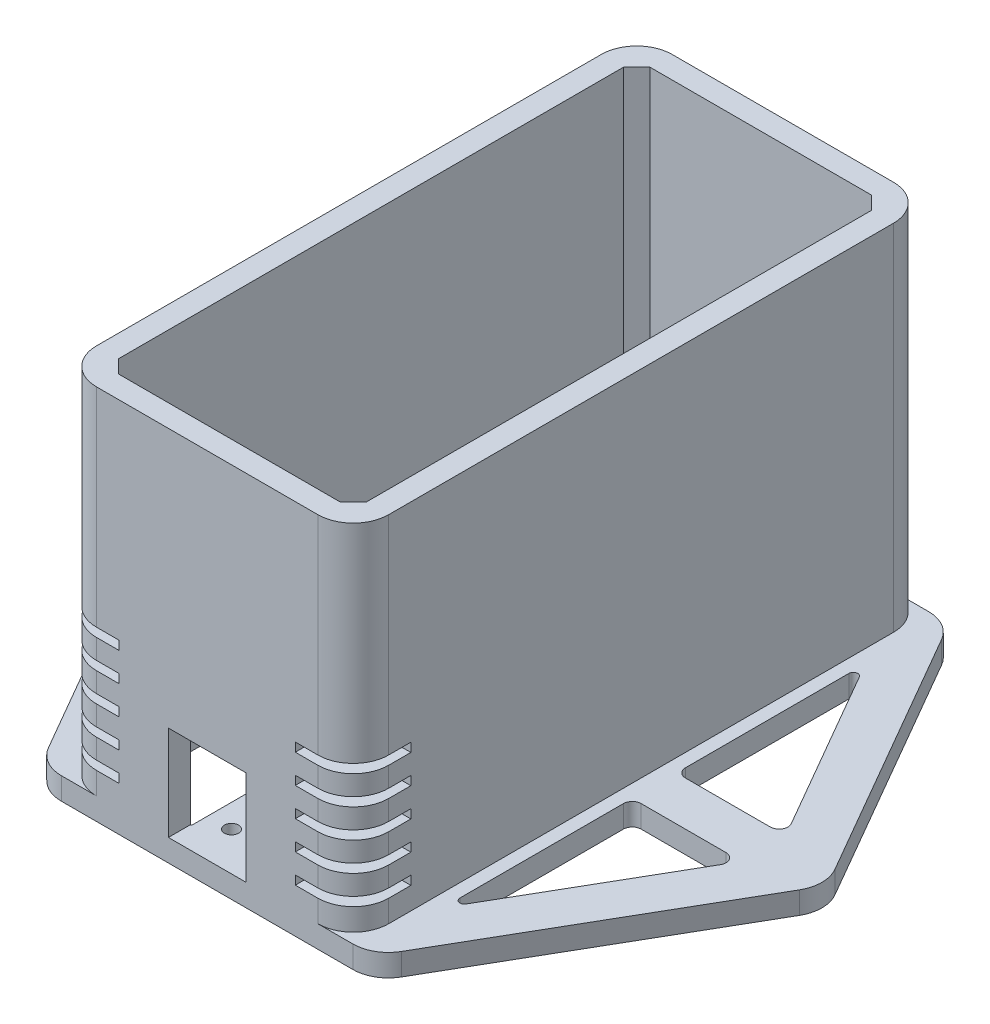
SolidWorks part; units mm, degrees
ref_plane "Front Plane" through (0, 0, 0) normal (0, 0, 1) x (1, 0, 0)
ref_plane "Top Plane" through (0, 0, 0) normal (0, 1, 0) x (1, 0, 0)
ref_plane "Right Plane" through (0, 0, 0) normal (1, 0, 0) x (0, 0, -1)
sketch "Sketch1" plane through (0, 0, 0) normal (0, 1, 0) x (1, 0, 0)
  line L1 (-75.0555, 0) -> (-37.5278, -65)
  line L2 (-37.5278, -65) -> (37.5278, -65)
  line L3 (37.5278, -65) -> (75.0555, 0)
  line L4 (75.0555, 0) -> (37.5278, 65)
  line L5 (37.5278, 65) -> (-37.5278, 65)
  line L6 (-37.5278, 65) -> (-75.0555, 0)
  circle A0 centre (0, 0) radius 65 construction
  circle A1 centre (0, 0) radius 50 construction
  dimension "D2" = 100
  dimension "D1" = 130
extrude "Boss-Extrude1" add sketch "Sketch1" along normal blind 5
fillet "Fillet1" radius 8 6 edges at (37.5278, 2.5, -65) (75.0555, 2.5, 0) (37.5278, 2.5, 65) (-37.5278, 2.5, 65) (-75.0555, 2.5, 0) (-37.5278, 2.5, -65)
sketch "Sketch3" plane through (0, 5, 0) normal (0, 1, 0) x (1, 0, 0)
  line L0 (-32.909, -65) -> (32.909, -65) construction
  line L1 (-25, 65) -> (25, 65)
  line L2 (-33, 57) -> (-33, -57)
  line L3 (-25, -65) -> (25, -65)
  line L4 (33, 57) -> (33, -57)
  line L5 (-33, 65) -> (33, -65) construction
  line L6 (-33, -65) -> (33, 65) construction
  arc A0 (33, 57) -> (25, 65) centre (25, 57) ccw
  arc A1 (33, -57) -> (25, -65) centre (25, -57) cw
  arc A2 (-25, -65) -> (-33, -57) centre (-25, -57) cw
  arc A3 (-25, 65) -> (-33, 57) centre (-25, 57) ccw
  point P0 (0, 0)
  dimension "D1" = 8
  dimension "D2" = 50
extrude "Boss-Extrude2" add sketch "Sketch3" along normal blind 80
sketch "Sketch4" plane through (0, 85, 0) normal (0, 1, 0) x (1, 0, 0)
  line L0 (-28, 57) -> (-25, 60)
  line L1 (25, 60) -> (28, 57)
  line L2 (28, -57) -> (25, -60)
  line L3 (-28, -57) -> (-25, -60)
  line L9 (-25, -60) -> (25, -60)
  line L10 (28, -57) -> (28, 57)
  line L11 (25, 60) -> (-25, 60)
  line L12 (-28, 57) -> (-28, -57)
  line L13 (-25, -60) -> (25, -60)
  line L14 (28, -57) -> (28, 57)
  line L15 (25, 60) -> (-25, 60)
  line L16 (-28, 57) -> (-28, -57)
  arc A9 (-28, -57) -> (-25, -60) centre (-25, -57) ccw
  arc A10 (25, -60) -> (28, -57) centre (25, -57) ccw
  arc A11 (28, 57) -> (25, 60) centre (25, 57) ccw
  arc A12 (-25, 60) -> (-28, 57) centre (-25, 57) ccw
  dimension "D1" = 5
extrude "Cut-Extrude1" cut sketch "Sketch4" against normal up to surface (85 mm away) up to face at (0, 0, 0)
sketch "Sketch8" plane through (0, 0, 0) normal (0, 1, 0) x (1, 0, 0)
  line L0 (0, 40) -> (0, 25) construction
  line L1 (0, 55) -> (0, 65) construction
  line L2 (9.5263, 26.5) -> (24.2487, 52) construction
  line L3 (22.5167, 55) -> (-22.5167, 55) construction
  line L4 (-24.2487, 52) -> (-9.5263, 26.5) construction
  line L5 (-12.5, 0) -> (-62.3346, 0) construction
  line L36 (6.9282, 25) -> (-6.9282, 25) construction
  line L37 (27.7128, 5) -> (57.1577, 5) construction
  line L38 (58.8897, 8) -> (36.3731, 47) construction
  line L39 (32.909, 47) -> (18.1865, 21.5) construction
  line L40 (25.1147, 6.5) -> (18.1865, 18.5) construction
  line L41 (18.1865, -21.5) -> (32.909, -47) construction
  line L42 (36.3731, -47) -> (58.8897, -8) construction
  line L43 (57.1577, -5) -> (27.7128, -5) construction
  line L44 (18.1865, -18.5) -> (25.1147, -6.5) construction
  line L45 (-9.5263, -26.5) -> (-24.2487, -52) construction
  line L46 (-22.5167, -55) -> (22.5167, -55) construction
  line L47 (24.2487, -52) -> (9.5263, -26.5) construction
  line L48 (-6.9282, -25) -> (6.9282, -25) construction
  line L49 (-27.7128, -5) -> (-57.1577, -5) construction
  line L50 (-58.8897, -8) -> (-36.3731, -47) construction
  line L51 (-32.909, -47) -> (-18.1865, -21.5) construction
  line L52 (-25.1147, -6.5) -> (-18.1865, -18.5) construction
  line L53 (-18.1865, 21.5) -> (-32.909, 47) construction
  line L54 (-37.866, 44.4141) -> (-58.8897, 8)
  line L55 (-57.1577, 5) -> (-38, 5)
  line L56 (-18.1865, 18.5) -> (-25.1147, 6.5) construction
  line L57 (-36, 7) -> (-36, 43.9141)
  line L58 (-33, 57) -> (-33, -57) construction
  line L59 (-36, -7) -> (-36, -43.9141)
  line L60 (-36.3731, 47) -> (-36, 47.6462) construction
  line L61 (-36, 5) -> (-27.7128, 5) construction
  line L71 (-33, 57) -> (-33, -57) construction
  line L72 (-57.1577, -5) -> (-38, -5)
  line L73 (-37.866, -44.4141) -> (-58.8897, -8)
  line L74 (37.866, -44.4141) -> (58.8897, -8)
  line L75 (57.1577, -5) -> (38, -5)
  line L76 (36, -7) -> (36, -43.9141)
  line L77 (36, 7) -> (36, 43.9141)
  line L78 (57.1577, 5) -> (38, 5)
  line L79 (37.866, 44.4141) -> (58.8897, 8)
  circle A0 centre (0, 0) radius 12.5 construction
  circle A1 centre (0, 40) radius 15 construction
  arc A3 (-22.5167, 55) -> (-24.2487, 52) centre (-22.5167, 53) ccw
  arc A4 (24.2487, 52) -> (22.5167, 55) centre (22.5167, 53) ccw construction
  arc A5 (6.9282, 25) -> (9.5263, 26.5) centre (6.9282, 28) ccw construction
  arc A6 (-6.9282, 25) -> (-9.5263, 26.5) centre (-6.9282, 28) cw construction
  arc A7 (25.1147, 6.5) -> (27.7128, 5) centre (27.7128, 8) ccw construction
  arc A8 (57.1577, 5) -> (58.8897, 8) centre (57.1577, 7) ccw construction
  arc A9 (36.3731, 47) -> (32.909, 47) centre (34.641, 46) ccw construction
  arc A10 (18.1865, 18.5) -> (18.1865, 21.5) centre (20.7846, 20) cw construction
  arc A11 (18.1865, -18.5) -> (18.1865, -21.5) centre (20.7846, -20) ccw construction
  arc A12 (32.909, -47) -> (36.3731, -47) centre (34.641, -46) ccw construction
  arc A13 (58.8897, -8) -> (57.1577, -5) centre (57.1577, -7) ccw construction
  arc A14 (25.1147, -6.5) -> (27.7128, -5) centre (27.7128, -8) cw construction
  arc A15 (-6.9282, -25) -> (-9.5263, -26.5) centre (-6.9282, -28) ccw construction
  arc A16 (-24.2487, -52) -> (-22.5167, -55) centre (-22.5167, -53) ccw construction
  arc A17 (22.5167, -55) -> (24.2487, -52) centre (22.5167, -53) ccw construction
  arc A18 (6.9282, -25) -> (9.5263, -26.5) centre (6.9282, -28) cw construction
  arc A19 (-25.1147, -6.5) -> (-27.7128, -5) centre (-27.7128, -8) ccw construction
  arc A20 (-57.1577, -5) -> (-58.8897, -8) centre (-57.1577, -7) ccw construction
  arc A21 (-36.3731, -47) -> (-32.909, -47) centre (-34.641, -46) ccw construction
  arc A22 (-18.1865, -18.5) -> (-18.1865, -21.5) centre (-20.7846, -20) cw construction
  arc A23 (-18.1865, 18.5) -> (-18.1865, 21.5) centre (-20.7846, 20) ccw construction
  arc A24 (-32.909, 47) -> (-36.3731, 47) centre (-34.641, 46) ccw construction
  arc A25 (-58.8897, 8) -> (-57.1577, 5) centre (-57.1577, 7) ccw
  arc A26 (-25.1147, 6.5) -> (-27.7128, 5) centre (-27.7128, 8) cw construction
  arc A28 (57.1577, -5) -> (58.8897, -8) centre (57.1577, -7) cw construction
  arc A31 (-36, 7) -> (-38, 5) centre (-38, 7) cw
  arc A32 (-36, 43.9141) -> (-37.866, 44.4141) centre (-37, 43.9141) ccw
  arc A33 (-36, -43.9141) -> (-37.866, -44.4141) centre (-37, -43.9141) cw
  arc A34 (-36, -7) -> (-38, -5) centre (-38, -7) ccw
  arc A35 (-58.8897, -8) -> (-57.1577, -5) centre (-57.1577, -7) cw
  arc A36 (57.1577, -5) -> (58.8897, -8) centre (57.1577, -7) cw construction
  arc A37 (58.8897, -8) -> (57.1577, -5) centre (57.1577, -7) ccw
  arc A38 (36, -7) -> (38, -5) centre (38, -7) cw
  arc A39 (36, -43.9141) -> (37.866, -44.4141) centre (37, -43.9141) ccw
  arc A40 (36, 43.9141) -> (37.866, 44.4141) centre (37, 43.9141) cw
  arc A41 (36, 7) -> (38, 5) centre (38, 7) ccw
  arc A42 (58.8897, 8) -> (57.1577, 5) centre (57.1577, 7) cw
  point P19 (0, 25)
  point P30 (0, 0)
  point P66 (0, 0)
  point P88 (0, 0)
  dimension "D1" = 25
  dimension "D3" = 30
  dimension "D6" = 2
  dimension "D8" = 3
  dimension "D11" = 2
  dimension "D12" = 1
  dimension "D2" = 40
  dimension "D4" = 10
  dimension "D5" = 15
  dimension "D7" = 25
  dimension "D9" = 3
extrude "Cut-Extrude2" cut sketch "Sketch8" along normal up to surface (5 mm away) contours A32 | L54 A25 L55 L57 | A35 L73 A33 L59 A34 L72 | L76 A39 L74 A37 L75 A38 | A42 L79 A40 L77 A41 L78 region at (-44.1761, 0, -19.1857) region at (-44.1761, 0, 19.1857) region at (44.1761, 0, 19.1857) region at (44.1761, 0, -19.1857) up to face at (-41.2442, 5, 0)
ref_plane "Plane1" through (0, 10, 0) normal (0, 1, 0) x (1, 0, 0)
sketch "Sketch9" plane through (0, 10, 0) normal (0, 1, 0) x (1, 0, 0)
  line L0 (-32.909, -65) -> (-33.909, -65) construction
  line L6 (-33.909, -65) -> (-19.909, -65)
  line L7 (-33.909, -65) -> (-33.909, -52)
  line L8 (-33.909, -52) -> (-19.909, -52)
  line L9 (-19.909, -65) -> (-19.909, -52)
  line L10 (-33.909, -65) -> (-19.909, -52) construction
  line L11 (-33.909, -52) -> (-19.909, -65) construction
  point P7 (-26.909, -58.5)
  dimension "D1" = 1
  dimension "D2" = 13
  dimension "D3" = 14
extrude "Cut-Extrude3" cut sketch "Sketch9" along normal blind 2
pattern_linear "LPattern1" count 5 spacing 6.5 along (0, 1, 0) of "Cut-Extrude3"
mirror "Mirror1" about plane through (0, 0, 0) normal (1, 0, 0) of "LPattern1"
sketch "Sketch10" plane through (0, 0, -60) normal (0, 0, 1) x (1, 0, 0)
  line L0 (-25, 0) -> (25, 0) construction
  line L1 (-8.5, 0) -> (8.5, 0)
  line L3 (-8.5, 5) -> (8.5, 5)
  line L4 (8.5, 0) -> (8.5, 5)
  line L5 (0, 0) -> (8.5, 5) construction
  line L6 (0, 5) -> (8.5, 0) construction
  line L7 (0, 0) -> (0, 5) construction
  line L8 (0, 5) -> (-8.5, 0) construction
  line L9 (0, 0) -> (-8.5, 5) construction
  line L10 (-8.5, 0) -> (-8.5, 5)
  point P4 (4.25, 2.5)
  point P9 (-4.25, 2.5)
  dimension "D1" = 8.5
extrude "Boss-Extrude3" add sketch "Sketch10" along normal up to surface (15 mm away)
sketch "Sketch11" plane through (0, 0, 0) normal (0, -1, 0) x (1, 0, 0)
  line L0 (3.25, -48.75) -> (8.5, -48.75) construction
  line L1 (3.25, -48.75) -> (3.25, -45) construction
  line L2 (0, -60) -> (0, -45) construction
  line L3 (-12.5, -52.5) -> (12.5, -52.5) construction
  line L4 (-8.5, -60) -> (8.5, -60) construction
  line L5 (-8.5, -45) -> (8.5, -45) construction
  line L6 (8.5, -45) -> (-8.5, -45) construction
  circle A0 centre (3.25, -56.25) radius 1.6
  circle A1 centre (-3.25, -56.25) radius 1.6
  circle A2 centre (-3.25, -48.75) radius 1.6
  circle A3 centre (3.25, -48.75) radius 1.6
  circle A4 centre (-3.25, -56.25) radius 3 construction
  dimension "D3" = 3.2
  dimension "D1" = 5.25
  dimension "D2" = 3.75
extrude "Cut-Extrude4" cut sketch "Sketch11" against normal blind 5
sketch "Sketch12" plane through (0, 0, -60) normal (0, 0, 1) x (1, 0, 0)
  line L0 (0, 0) -> (0, 5) construction
  line L1 (8.5, 0) -> (-8.5, 0) construction
  line L2 (-8.5, 5) -> (8.5, 5) construction
  line L3 (8.75, 5) -> (-8.75, 5)
  line L4 (-8.75, 5) -> (-8.75, 26.4)
  line L5 (-8.75, 26.4) -> (8.75, 26.4)
  line L6 (8.75, 5) -> (8.75, 26.4)
  point P10 (0, 26.4)
  dimension "D1" = 8.75
  dimension "D2" = 21.4
extrude "Cut-Extrude5" cut sketch "Sketch12" against normal up to surface and the other way up to surface up to face at (0, 23.75, -65) other way up to face at (0, 23.9583, 65)
sketch "Sketch14" plane through (0, 0, 60) normal (0, 0, -1) x (-1, 0, 0)
  line L0 (0, 0) -> (8.5, 0) construction
  line L1 (-25, 0) -> (25, 0) construction
  line L3 (8.5, 0) -> (-8.5, 0)
  line L4 (8.5, 0) -> (8.5, 5)
  line L5 (8.5, 5) -> (-8.5, 5)
  line L6 (-8.5, 0) -> (-8.5, 5)
  line L7 (8.5, 0) -> (-8.5, 5) construction
  line L8 (8.5, 5) -> (-8.5, 0) construction
  point P7 (0, 2.5)
extrude "Boss-Extrude4" add sketch "Sketch14" along normal up to surface (15 mm away)
sketch "Sketch16" plane through (0, 0, 0) normal (0, -1, 0) x (1, 0, 0)
  line L0 (3.25, 56.25) -> (8.5, 56.25) construction
  line L1 (3.25, 56.25) -> (3.25, 60) construction
  line L2 (0, 45) -> (0, 60) construction
  line L3 (-12.5, 52.5) -> (12.5, 52.5) construction
  line L4 (-8.5, 45) -> (8.5, 45) construction
  line L5 (8.5, 45) -> (-8.5, 45) construction
  line L6 (-3.25, 48.75) -> (-3.25, 45) construction
  line L7 (-3.25, 48.75) -> (-8.5, 48.75) construction
  line L8 (8.5, 45) -> (-8.5, 45) construction
  line L9 (-8.5, 45) -> (8.5, 45) construction
  line L10 (8.5, 45) -> (8.5, 60) construction
  line L11 (-8.5, 45) -> (-8.5, 60) construction
  circle A0 centre (3.25, 48.75) radius 1.6
  circle A1 centre (-3.25, 48.75) radius 1.6
  circle A2 centre (-3.25, 56.25) radius 1.6
  circle A3 centre (3.25, 56.25) radius 1.6
  circle A4 centre (-3.25, 48.75) radius 3 construction
  dimension "D1" = 3.2
  dimension "D2" = 5.25
  dimension "D3" = 3.75
extrude "Cut-Extrude6" cut sketch "Sketch16" against normal blind 5
